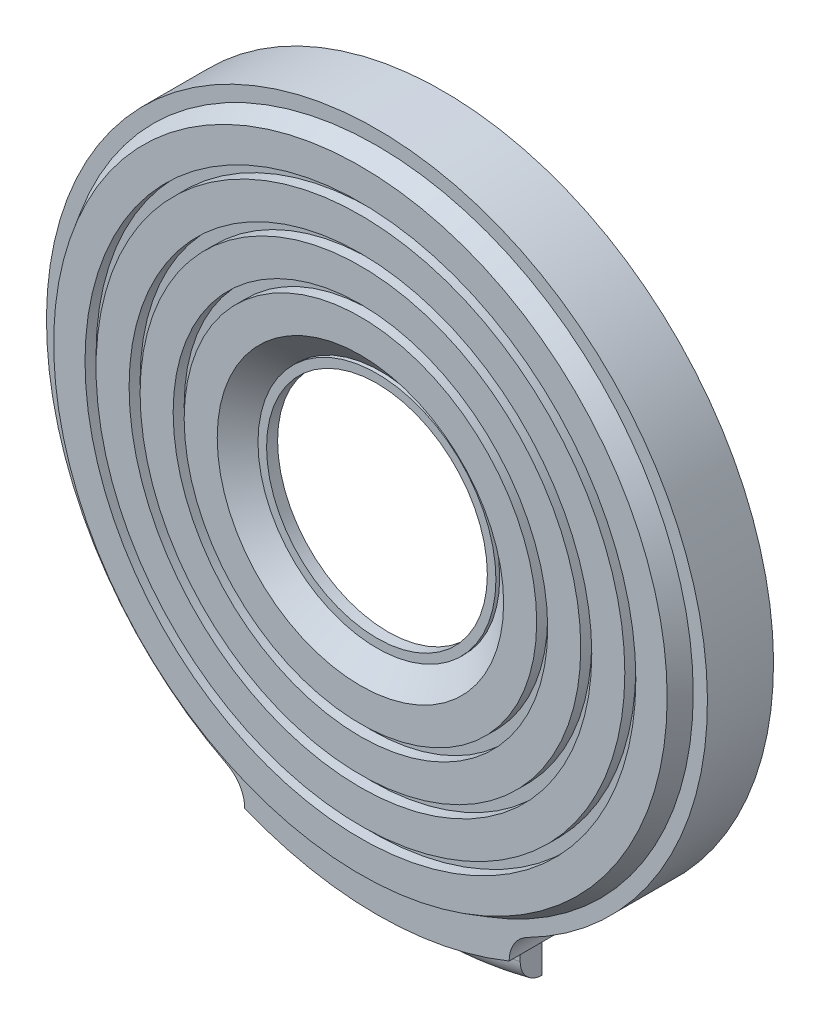
SolidWorks part; units mm, degrees
ref_plane "Front Plane" through (0, 0, 0) normal (0, 0, 1) x (1, 0, 0)
ref_plane "Top Plane" through (0, 0, 0) normal (0, 1, 0) x (1, 0, 0)
ref_plane "Right Plane" through (0, 0, 0) normal (1, 0, 0) x (0, 0, -1)
sketch "草图2" plane through (0, 0, 20) normal (0, 0, 1) x (1, 0, 0)
  line L2 (12, -35.4955) -> (12, -29.3939)
  line L3 (-12, -29.3939) -> (-12, -35.4955)
  arc A0 (13.6364, -26.7217) -> (-13.6364, -26.7217) centre (0, 0) ccw
  circle A1 centre (0, 0) radius 26.9356
  arc A5 (13.6364, -26.7217) -> (12, -29.3939) centre (15, -29.3939) ccw
  arc A6 (-12, -35.4955) -> (12, -35.4955) centre (0, 0) ccw
  arc A7 (-12, -29.3939) -> (-13.6364, -26.7217) centre (-15, -29.3939) ccw
extrude "凸台-拉伸1" add sketch "草图2" along normal blind 2
sketch "草图3" plane through (0, 0, 22) normal (0, 0, 1) x (1, 0, 0)
  line L0 (-9, -36.3721) -> (-9, -28.6182)
  line L1 (0, -37.469) -> (0, -24.2396) construction
  line L2 (9, -36.3721) -> (9, -28.6182)
  line L3 (12, -35.4955) -> (12, -29.3939) construction
  line L4 (-12, -29.3939) -> (-12, -35.4955) construction
  line L5 (12, -35.4955) -> (12, -29.3939)
  line L6 (-12, -29.3939) -> (-12, -35.4955)
  arc A0 (-12, -35.4955) -> (12, -35.4955) centre (0, 0) ccw construction
  circle A1 centre (0, 0) radius 30 construction
  arc A2 (-13.6364, -26.7217) -> (-9, -28.6182) centre (0, 0) ccw
  arc A4 (13.6364, -26.7217) -> (12, -29.3939) centre (15, -29.3939) ccw construction
  arc A5 (-12, -29.3939) -> (-13.6364, -26.7217) centre (-15, -29.3939) ccw construction
  arc A6 (13.6364, -26.7217) -> (12, -29.3939) centre (15, -29.3939) ccw
  arc A7 (-12, -35.4955) -> (-9, -36.3721) centre (0, 0) ccw
  arc A8 (-12, -29.3939) -> (-13.6364, -26.7217) centre (-15, -29.3939) ccw
  arc A9 (9, -28.6182) -> (13.6364, -26.7217) centre (0, 0) ccw
  arc A10 (9, -36.3721) -> (12, -35.4955) centre (0, 0) ccw
  dimension "D1" = 9
extrude "切除-拉伸3" cut sketch "草图3" against normal blind 2
sketch "草图4" plane through (0, 0, 22) normal (0, 0, 1) x (1, 0, 0)
  line L0 (9, -28.6182) -> (9, -36.3721) construction
  line L1 (-9, -36.3721) -> (-9, -28.6182) construction
  line L6 (9, -35) -> (9, -36.3721)
  line L7 (-9, -36.3721) -> (-9, -35)
  arc A0 (-9, -36.3721) -> (9, -36.3721) centre (0, 0) ccw construction
  arc A1 (-9, -36.3721) -> (9, -36.3721) centre (0, 0) ccw
  arc A5 (-9, -35) -> (9, -35) centre (0, 0) ccw
extrude "切除-拉伸4" cut sketch "草图4" against normal blind 2
fillet "圆角2" radius 2 1 edges at (0, -36.1386, 22)
sketch "草图7" plane through (0, 0, 22) normal (0, 0, 1) x (1, 0, 0)
  line L2 (-9, -28.6182) -> (-9, -32.9309)
  line L3 (9, -32.9309) -> (9, -28.6182)
  line L4 (-9, -30.4467) -> (-9, -32.9309)
  line L5 (9, -32.9309) -> (9, -30.4467)
  arc A0 (-12, -29.3939) -> (-13.6364, -26.7217) centre (-15, -29.3939) ccw construction
  arc A2 (-9, -32.9309) -> (9, -32.9309) centre (0, 0) ccw
  arc A3 (9, -28.6182) -> (-9, -28.6182) centre (0, 0) ccw
  arc A4 (-9, -32.9309) -> (9, -32.9309) centre (0, 0) ccw
  arc A5 (9, -28.6182) -> (13.6364, -26.7217) centre (0, 0) ccw
  arc A6 (13.6364, -26.7217) -> (12, -29.3939) centre (15, -29.3939) ccw construction
  arc A7 (13.6364, -26.7217) -> (12, -29.3939) centre (15, -29.3939) ccw
  arc A8 (9, -28.6182) -> (-9, -28.6182) centre (0, 0) ccw construction
  arc A9 (9, -28.6182) -> (13.6364, -26.7217) centre (0, 0) ccw
  arc A10 (13.6364, -26.7217) -> (12, -29.3939) centre (15, -29.3939) ccw
  arc A11 (-12, -29.3939) -> (-13.6364, -26.7217) centre (-15, -29.3939) ccw
  arc A12 (-12, -29.3939) -> (12, -29.3939) centre (0, 0) ccw
  arc A13 (-13.6364, -26.7217) -> (13.6364, -26.7217) centre (0, 0) ccw
  arc A14 (-13.6364, -26.7217) -> (-9, -28.6182) centre (0, 0) ccw
  arc A15 (-13.6364, -26.7217) -> (-9, -28.6182) centre (0, 0) ccw
  line M7 (-9, -28.6182) -> (-9, -32.9309)
  line M9 (9, -32.9309) -> (9, -28.6182)
  arc M10 (9, -28.6182) -> (-9, -28.6182) centre (0, 0) ccw
  dimension "D1" = 0
extrude "凸台-拉伸2" add sketch "草图7" against normal blind 2 contours A11 A12 M7 M10 | A13 A12 M7 M9 | A12 A7 M9 M10 region at (0, -30.4259, 22) region at (-10.6878, -28.8911, 22) region at (10.6878, -28.8911, 22)
sketch "草图8" plane through (0, 0, 22) normal (0, 0, 1) x (1, 0, 0)
  arc A0 (-12, -29.3939) -> (12, -29.3939) centre (0, 0) ccw
  arc A1 (13.6364, -26.7217) -> (12, -29.3939) centre (15, -29.3939) ccw construction
  circle A2 centre (0, 0) radius 30 construction
  arc A3 (-12, -29.3939) -> (-13.6364, -26.7217) centre (-15, -29.3939) ccw construction
  arc A4 (13.6364, -26.7217) -> (12, -29.3939) centre (15, -29.3939) ccw
  arc A5 (-13.6364, -26.7217) -> (13.6364, -26.7217) centre (0, 0) ccw
  arc A6 (-12, -29.3939) -> (-13.6364, -26.7217) centre (-15, -29.3939) ccw
extrude "凸台-拉伸3" add sketch "草图8" along normal blind 4
sketch "草图9" plane through (0, 0, 22) normal (0, 0, 1) x (1, 0, 0)
  circle A3 centre (0, 0) radius 27
  circle A4 centre (0, 0) radius 30
extrude "凸台-拉伸5" add sketch "草图9" along normal blind 4
sketch "草图10" plane through (0, 0, 26) normal (0, 0, 1) x (1, 0, 0)
  circle A0 centre (0, 0) radius 29
extrude "凸台-拉伸6" add sketch "草图10" along normal up to surface (1.5 mm away)
chamfer "倒角1" distance 2 angle 30 1 edges at (29, 0, 27.5) first distance on face at (29, 0, 26)
sketch "草图12" plane through (0, 0, 27.5) normal (0, 0, 1) x (1, 0, 0)
  circle A0 centre (0, 0) radius 10
extrude "切除-拉伸5" cut sketch "草图12" against normal blind 18
sketch "草图13" plane through (0, 0, 20) normal (0, 0, -1) x (-1, 0, 0)
  circle A0 centre (0, 0) radius 27
extrude "凸台-拉伸7" add sketch "草图13" against normal up to surface (6 mm away) up to face at (10, 0, 26)
sketch "草图14" plane through (0, 0, 27.5) normal (0, 0, 1) x (1, 0, 0)
  circle A0 centre (0, 0) radius 10
extrude "切除-拉伸6" cut sketch "草图14" against normal blind 8
sketch "草图16" plane through (0, 0, 20) normal (0, 0, -1) x (-1, 0, 0)
  circle A0 centre (0, 0) radius 27
extrude "切除-拉伸7" cut sketch "草图16" against normal blind 5
chamfer "倒角2" distance 3 angle 40 1 edges at (10, 0, 27.5) first distance on face at (10, 0, 27.5)
sketch "草图17" plane through (0, 0, 27.5) normal (0, 0, 1) x (1, 0, 0)
  circle A0 centre (0, 0) radius 25
  circle A1 centre (0, 0) radius 24
  circle A2 centre (0, 0) radius 21
  circle A3 centre (0, 0) radius 20
  circle A4 centre (0, 0) radius 17
  circle A5 centre (0, 0) radius 16
  dimension "D1" = 50
  dimension "D2" = 48
  dimension "D3" = 42
  dimension "D4" = 40
  dimension "D5" = 34
  dimension "D6" = 32
extrude "切除-拉伸10" cut sketch "草图17" against normal blind 1 contours A0 A1 | A2 A3 | A4 A5 region at (-24.2929, 0, 27.5) region at (-20.406, 0, 27.5) region at (-16.5192, 0, 27.5)
sketch "草图18" plane through (0, 0, 0) normal (0, 1, 0) x (1, 0, 0)
  line L0 (0, -20) -> (0, -40.9012) construction
  line L1 (-10.5, -23.7655) -> (-7.5, -23.7655)
  line L2 (-10.5, -23.7655) -> (-10.5, -22.7655)
  line L3 (-4.5, -23.7655) -> (-1.5, -23.7655)
  line L4 (-4.5, -23.7655) -> (-4.5, -22.7655)
  line L5 (-4.5, -22.7655) -> (-1.5, -22.7655)
  line L6 (-1.5, -23.7655) -> (-1.5, -22.7655)
  line L7 (-10.5, -22.7655) -> (-7.5, -22.7655)
  line L8 (-7.5, -23.7655) -> (-7.5, -22.7655)
  line L9 (7.5, -23.7655) -> (7.5, -22.7655)
  line L10 (10.5, -22.7655) -> (7.5, -22.7655)
  line L11 (1.5, -23.7655) -> (1.5, -22.7655)
  line L12 (4.5, -22.7655) -> (1.5, -22.7655)
  line L13 (4.5, -23.7655) -> (4.5, -22.7655)
  line L14 (4.5, -23.7655) -> (1.5, -23.7655)
  line L15 (10.5, -23.7655) -> (10.5, -22.7655)
  line L16 (10.5, -23.7655) -> (7.5, -23.7655)
  dimension "D1" = 1.5
  dimension "D2" = 2
extrude "切除-拉伸11" cut sketch "草图18" against normal blind 71
sketch "草图25" plane through (0, 0, 25) normal (0, 0, -1) x (-1, 0, 0)
  circle A0 centre (0, 0) radius 10.0206
  circle A1 centre (0, 0) radius 10.8
extrude "凸台-拉伸18" add sketch "草图25" against normal blind 1
